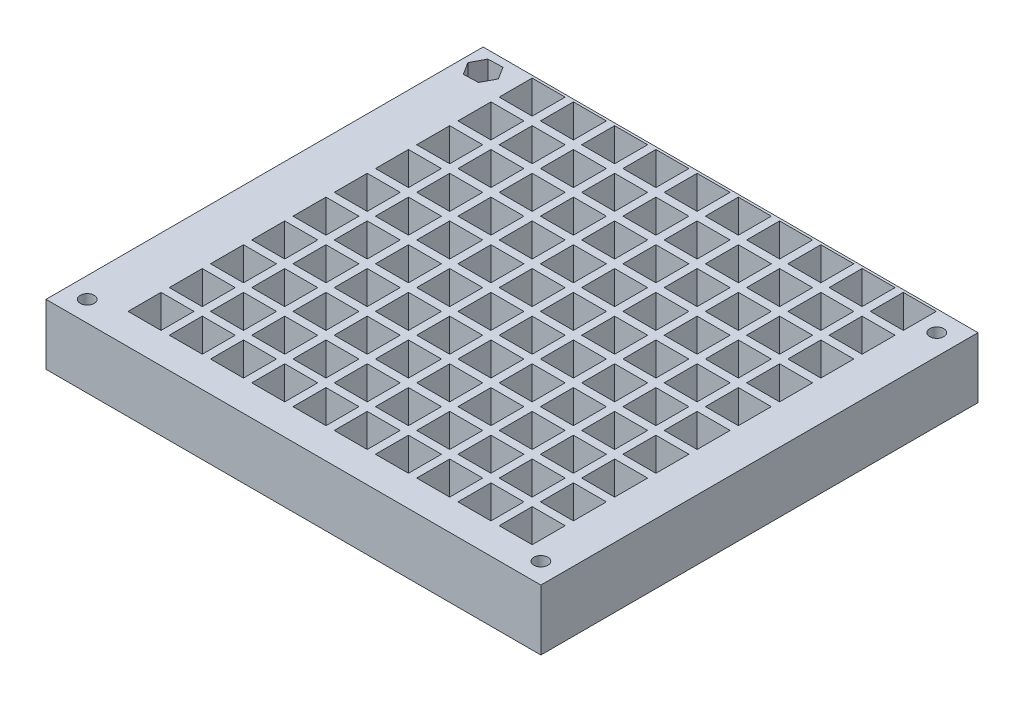
SolidWorks part; units mm, degrees
ref_plane "Front Plane" through (0, 0, 0) normal (0, 0, 1) x (1, 0, 0)
ref_plane "Top Plane" through (0, 0, 0) normal (0, 1, 0) x (1, 0, 0)
ref_plane "Right Plane" through (0, 0, 0) normal (1, 0, 0) x (0, 0, -1)
sketch "Sketch1" plane through (0, 0, 0) normal (0, 1, 0) x (1, 0, 0)
  line L0 (115, 101) -> (5, 101) construction
  line L1 (0, 0) -> (120, 0)
  line L2 (0, 0) -> (0, 106)
  line L3 (0, 106) -> (120, 106)
  line L4 (120, 0) -> (120, 106)
  line L6 (115, 101) -> (115, 5) construction
  line L8 (6.8918, 97.9769) -> (8.564, 101.1268)
  line L9 (8.564, 101.1268) -> (6.6722, 104.1499)
  line L10 (6.6722, 104.1499) -> (3.1082, 104.0231)
  line L11 (3.1082, 104.0231) -> (1.436, 100.8732)
  line L12 (1.436, 100.8732) -> (3.3278, 97.8501)
  line L13 (3.3278, 97.8501) -> (6.8918, 97.9769)
  line L14 (22.4764, 15.4138) -> (22.4764, 7.4138)
  line L15 (12.4764, 15.4138) -> (20.4764, 15.4138)
  line L16 (12.4764, 15.4138) -> (12.4764, 7.4138)
  line L17 (12.4764, 7.4138) -> (20.4764, 7.4138)
  line L18 (20.4764, 15.4138) -> (20.4764, 7.4138)
  line L19 (22.4764, 15.4138) -> (30.4764, 15.4138)
  line L20 (30.4764, 15.4138) -> (30.4764, 7.4138)
  line L21 (22.4764, 7.4138) -> (30.4764, 7.4138)
  line L22 (32.4764, 15.4138) -> (32.4764, 7.4138)
  line L23 (32.4764, 15.4138) -> (40.4764, 15.4138)
  line L24 (40.4764, 15.4138) -> (40.4764, 7.4138)
  line L25 (32.4764, 7.4138) -> (40.4764, 7.4138)
  line L26 (42.4764, 15.4138) -> (42.4764, 7.4138)
  line L27 (42.4764, 15.4138) -> (50.4764, 15.4138)
  line L28 (50.4764, 15.4138) -> (50.4764, 7.4138)
  line L29 (42.4764, 7.4138) -> (50.4764, 7.4138)
  line L30 (52.4764, 15.4138) -> (52.4764, 7.4138)
  line L31 (52.4764, 15.4138) -> (60.4764, 15.4138)
  line L32 (60.4764, 15.4138) -> (60.4764, 7.4138)
  line L33 (52.4764, 7.4138) -> (60.4764, 7.4138)
  line L34 (62.4764, 15.4138) -> (62.4764, 7.4138)
  line L35 (62.4764, 15.4138) -> (70.4764, 15.4138)
  line L36 (70.4764, 15.4138) -> (70.4764, 7.4138)
  line L37 (62.4764, 7.4138) -> (70.4764, 7.4138)
  line L38 (72.4764, 15.4138) -> (72.4764, 7.4138)
  line L39 (72.4764, 15.4138) -> (80.4764, 15.4138)
  line L40 (80.4764, 15.4138) -> (80.4764, 7.4138)
  line L41 (72.4764, 7.4138) -> (80.4764, 7.4138)
  line L42 (82.4764, 15.4138) -> (82.4764, 7.4138)
  line L43 (82.4764, 15.4138) -> (90.4764, 15.4138)
  line L44 (90.4764, 15.4138) -> (90.4764, 7.4138)
  line L45 (82.4764, 7.4138) -> (90.4764, 7.4138)
  line L46 (92.4764, 15.4138) -> (92.4764, 7.4138)
  line L47 (92.4764, 15.4138) -> (100.4764, 15.4138)
  line L48 (100.4764, 15.4138) -> (100.4764, 7.4138)
  line L49 (92.4764, 7.4138) -> (100.4764, 7.4138)
  line L50 (102.4764, 15.4138) -> (102.4764, 7.4138)
  line L51 (102.4764, 15.4138) -> (110.4764, 15.4138)
  line L52 (110.4764, 15.4138) -> (110.4764, 7.4138)
  line L53 (102.4764, 7.4138) -> (110.4764, 7.4138)
  line L54 (22.4764, 25.4138) -> (22.4764, 17.4138)
  line L55 (22.4764, 25.4138) -> (30.4764, 25.4138)
  line L56 (30.4764, 25.4138) -> (30.4764, 17.4138)
  line L57 (22.4764, 17.4138) -> (30.4764, 17.4138)
  line L58 (32.4764, 25.4138) -> (32.4764, 17.4138)
  line L59 (32.4764, 25.4138) -> (40.4764, 25.4138)
  line L60 (40.4764, 25.4138) -> (40.4764, 17.4138)
  line L61 (32.4764, 17.4138) -> (40.4764, 17.4138)
  line L62 (42.4764, 25.4138) -> (42.4764, 17.4138)
  line L63 (42.4764, 25.4138) -> (50.4764, 25.4138)
  line L64 (50.4764, 25.4138) -> (50.4764, 17.4138)
  line L65 (42.4764, 17.4138) -> (50.4764, 17.4138)
  line L66 (52.4764, 25.4138) -> (52.4764, 17.4138)
  line L67 (52.4764, 25.4138) -> (60.4764, 25.4138)
  line L68 (60.4764, 25.4138) -> (60.4764, 17.4138)
  line L69 (52.4764, 17.4138) -> (60.4764, 17.4138)
  line L70 (62.4764, 25.4138) -> (62.4764, 17.4138)
  line L71 (62.4764, 25.4138) -> (70.4764, 25.4138)
  line L72 (70.4764, 25.4138) -> (70.4764, 17.4138)
  line L73 (62.4764, 17.4138) -> (70.4764, 17.4138)
  line L74 (72.4764, 25.4138) -> (72.4764, 17.4138)
  line L75 (72.4764, 25.4138) -> (80.4764, 25.4138)
  line L76 (80.4764, 25.4138) -> (80.4764, 17.4138)
  line L77 (72.4764, 17.4138) -> (80.4764, 17.4138)
  line L78 (82.4764, 25.4138) -> (82.4764, 17.4138)
  line L79 (82.4764, 25.4138) -> (90.4764, 25.4138)
  line L80 (90.4764, 25.4138) -> (90.4764, 17.4138)
  line L81 (82.4764, 17.4138) -> (90.4764, 17.4138)
  line L82 (92.4764, 25.4138) -> (92.4764, 17.4138)
  line L83 (92.4764, 25.4138) -> (100.4764, 25.4138)
  line L84 (100.4764, 25.4138) -> (100.4764, 17.4138)
  line L85 (92.4764, 17.4138) -> (100.4764, 17.4138)
  line L86 (102.4764, 25.4138) -> (102.4764, 17.4138)
  line L87 (102.4764, 25.4138) -> (110.4764, 25.4138)
  line L88 (110.4764, 25.4138) -> (110.4764, 17.4138)
  line L89 (102.4764, 17.4138) -> (110.4764, 17.4138)
  line L90 (22.4764, 35.4138) -> (22.4764, 27.4138)
  line L91 (22.4764, 35.4138) -> (30.4764, 35.4138)
  line L92 (30.4764, 35.4138) -> (30.4764, 27.4138)
  line L93 (22.4764, 27.4138) -> (30.4764, 27.4138)
  line L94 (32.4764, 35.4138) -> (32.4764, 27.4138)
  line L95 (32.4764, 35.4138) -> (40.4764, 35.4138)
  line L96 (40.4764, 35.4138) -> (40.4764, 27.4138)
  line L97 (32.4764, 27.4138) -> (40.4764, 27.4138)
  line L98 (42.4764, 35.4138) -> (42.4764, 27.4138)
  line L99 (42.4764, 35.4138) -> (50.4764, 35.4138)
  line L100 (50.4764, 35.4138) -> (50.4764, 27.4138)
  line L101 (42.4764, 27.4138) -> (50.4764, 27.4138)
  line L102 (52.4764, 35.4138) -> (52.4764, 27.4138)
  line L103 (52.4764, 35.4138) -> (60.4764, 35.4138)
  line L104 (60.4764, 35.4138) -> (60.4764, 27.4138)
  line L105 (52.4764, 27.4138) -> (60.4764, 27.4138)
  line L106 (62.4764, 35.4138) -> (62.4764, 27.4138)
  line L107 (62.4764, 35.4138) -> (70.4764, 35.4138)
  line L108 (70.4764, 35.4138) -> (70.4764, 27.4138)
  line L109 (62.4764, 27.4138) -> (70.4764, 27.4138)
  line L110 (72.4764, 35.4138) -> (72.4764, 27.4138)
  line L111 (72.4764, 35.4138) -> (80.4764, 35.4138)
  line L112 (80.4764, 35.4138) -> (80.4764, 27.4138)
  line L113 (72.4764, 27.4138) -> (80.4764, 27.4138)
  line L114 (82.4764, 35.4138) -> (82.4764, 27.4138)
  line L115 (82.4764, 35.4138) -> (90.4764, 35.4138)
  line L116 (90.4764, 35.4138) -> (90.4764, 27.4138)
  line L117 (82.4764, 27.4138) -> (90.4764, 27.4138)
  line L118 (92.4764, 35.4138) -> (92.4764, 27.4138)
  line L119 (92.4764, 35.4138) -> (100.4764, 35.4138)
  line L120 (100.4764, 35.4138) -> (100.4764, 27.4138)
  line L121 (92.4764, 27.4138) -> (100.4764, 27.4138)
  line L122 (102.4764, 35.4138) -> (102.4764, 27.4138)
  line L123 (102.4764, 35.4138) -> (110.4764, 35.4138)
  line L124 (110.4764, 35.4138) -> (110.4764, 27.4138)
  line L125 (102.4764, 27.4138) -> (110.4764, 27.4138)
  line L126 (22.4764, 45.4138) -> (22.4764, 37.4138)
  line L127 (22.4764, 45.4138) -> (30.4764, 45.4138)
  line L128 (30.4764, 45.4138) -> (30.4764, 37.4138)
  line L129 (22.4764, 37.4138) -> (30.4764, 37.4138)
  line L130 (32.4764, 45.4138) -> (32.4764, 37.4138)
  line L131 (32.4764, 45.4138) -> (40.4764, 45.4138)
  line L132 (40.4764, 45.4138) -> (40.4764, 37.4138)
  line L133 (32.4764, 37.4138) -> (40.4764, 37.4138)
  line L134 (42.4764, 45.4138) -> (42.4764, 37.4138)
  line L135 (42.4764, 45.4138) -> (50.4764, 45.4138)
  line L136 (50.4764, 45.4138) -> (50.4764, 37.4138)
  line L137 (42.4764, 37.4138) -> (50.4764, 37.4138)
  line L138 (52.4764, 45.4138) -> (52.4764, 37.4138)
  line L139 (52.4764, 45.4138) -> (60.4764, 45.4138)
  line L140 (60.4764, 45.4138) -> (60.4764, 37.4138)
  line L141 (52.4764, 37.4138) -> (60.4764, 37.4138)
  line L142 (62.4764, 45.4138) -> (62.4764, 37.4138)
  line L143 (62.4764, 45.4138) -> (70.4764, 45.4138)
  line L144 (70.4764, 45.4138) -> (70.4764, 37.4138)
  line L145 (62.4764, 37.4138) -> (70.4764, 37.4138)
  line L146 (72.4764, 45.4138) -> (72.4764, 37.4138)
  line L147 (72.4764, 45.4138) -> (80.4764, 45.4138)
  line L148 (80.4764, 45.4138) -> (80.4764, 37.4138)
  line L149 (72.4764, 37.4138) -> (80.4764, 37.4138)
  line L150 (82.4764, 45.4138) -> (82.4764, 37.4138)
  line L151 (82.4764, 45.4138) -> (90.4764, 45.4138)
  line L152 (90.4764, 45.4138) -> (90.4764, 37.4138)
  line L153 (82.4764, 37.4138) -> (90.4764, 37.4138)
  line L154 (92.4764, 45.4138) -> (92.4764, 37.4138)
  line L155 (92.4764, 45.4138) -> (100.4764, 45.4138)
  line L156 (100.4764, 45.4138) -> (100.4764, 37.4138)
  line L157 (92.4764, 37.4138) -> (100.4764, 37.4138)
  line L158 (102.4764, 45.4138) -> (102.4764, 37.4138)
  line L159 (102.4764, 45.4138) -> (110.4764, 45.4138)
  line L160 (110.4764, 45.4138) -> (110.4764, 37.4138)
  line L161 (102.4764, 37.4138) -> (110.4764, 37.4138)
  line L162 (22.4764, 55.4138) -> (22.4764, 47.4138)
  line L163 (22.4764, 55.4138) -> (30.4764, 55.4138)
  line L164 (30.4764, 55.4138) -> (30.4764, 47.4138)
  line L165 (22.4764, 47.4138) -> (30.4764, 47.4138)
  line L166 (32.4764, 55.4138) -> (32.4764, 47.4138)
  line L167 (32.4764, 55.4138) -> (40.4764, 55.4138)
  line L168 (40.4764, 55.4138) -> (40.4764, 47.4138)
  line L169 (32.4764, 47.4138) -> (40.4764, 47.4138)
  line L170 (42.4764, 55.4138) -> (42.4764, 47.4138)
  line L171 (42.4764, 55.4138) -> (50.4764, 55.4138)
  line L172 (50.4764, 55.4138) -> (50.4764, 47.4138)
  line L173 (42.4764, 47.4138) -> (50.4764, 47.4138)
  line L174 (52.4764, 55.4138) -> (52.4764, 47.4138)
  line L175 (52.4764, 55.4138) -> (60.4764, 55.4138)
  line L176 (60.4764, 55.4138) -> (60.4764, 47.4138)
  line L177 (52.4764, 47.4138) -> (60.4764, 47.4138)
  line L178 (62.4764, 55.4138) -> (62.4764, 47.4138)
  line L179 (62.4764, 55.4138) -> (70.4764, 55.4138)
  line L180 (70.4764, 55.4138) -> (70.4764, 47.4138)
  line L181 (62.4764, 47.4138) -> (70.4764, 47.4138)
  line L182 (72.4764, 55.4138) -> (72.4764, 47.4138)
  line L183 (72.4764, 55.4138) -> (80.4764, 55.4138)
  line L184 (80.4764, 55.4138) -> (80.4764, 47.4138)
  line L185 (72.4764, 47.4138) -> (80.4764, 47.4138)
  line L186 (82.4764, 55.4138) -> (82.4764, 47.4138)
  line L187 (82.4764, 55.4138) -> (90.4764, 55.4138)
  line L188 (90.4764, 55.4138) -> (90.4764, 47.4138)
  line L189 (82.4764, 47.4138) -> (90.4764, 47.4138)
  line L190 (92.4764, 55.4138) -> (92.4764, 47.4138)
  line L191 (92.4764, 55.4138) -> (100.4764, 55.4138)
  line L192 (100.4764, 55.4138) -> (100.4764, 47.4138)
  line L193 (92.4764, 47.4138) -> (100.4764, 47.4138)
  line L194 (102.4764, 55.4138) -> (102.4764, 47.4138)
  line L195 (102.4764, 55.4138) -> (110.4764, 55.4138)
  line L196 (110.4764, 55.4138) -> (110.4764, 47.4138)
  line L197 (102.4764, 47.4138) -> (110.4764, 47.4138)
  line L198 (22.4764, 65.4138) -> (22.4764, 57.4138)
  line L199 (22.4764, 65.4138) -> (30.4764, 65.4138)
  line L200 (30.4764, 65.4138) -> (30.4764, 57.4138)
  line L201 (22.4764, 57.4138) -> (30.4764, 57.4138)
  line L202 (32.4764, 65.4138) -> (32.4764, 57.4138)
  line L203 (32.4764, 65.4138) -> (40.4764, 65.4138)
  line L204 (40.4764, 65.4138) -> (40.4764, 57.4138)
  line L205 (32.4764, 57.4138) -> (40.4764, 57.4138)
  line L206 (42.4764, 65.4138) -> (42.4764, 57.4138)
  line L207 (42.4764, 65.4138) -> (50.4764, 65.4138)
  line L208 (50.4764, 65.4138) -> (50.4764, 57.4138)
  line L209 (42.4764, 57.4138) -> (50.4764, 57.4138)
  line L210 (52.4764, 65.4138) -> (52.4764, 57.4138)
  line L211 (52.4764, 65.4138) -> (60.4764, 65.4138)
  line L212 (60.4764, 65.4138) -> (60.4764, 57.4138)
  line L213 (52.4764, 57.4138) -> (60.4764, 57.4138)
  line L214 (62.4764, 65.4138) -> (62.4764, 57.4138)
  line L215 (62.4764, 65.4138) -> (70.4764, 65.4138)
  line L216 (70.4764, 65.4138) -> (70.4764, 57.4138)
  line L217 (62.4764, 57.4138) -> (70.4764, 57.4138)
  line L218 (72.4764, 65.4138) -> (72.4764, 57.4138)
  line L219 (72.4764, 65.4138) -> (80.4764, 65.4138)
  line L220 (80.4764, 65.4138) -> (80.4764, 57.4138)
  line L221 (72.4764, 57.4138) -> (80.4764, 57.4138)
  line L222 (82.4764, 65.4138) -> (82.4764, 57.4138)
  line L223 (82.4764, 65.4138) -> (90.4764, 65.4138)
  line L224 (90.4764, 65.4138) -> (90.4764, 57.4138)
  line L225 (82.4764, 57.4138) -> (90.4764, 57.4138)
  line L226 (92.4764, 65.4138) -> (92.4764, 57.4138)
  line L227 (92.4764, 65.4138) -> (100.4764, 65.4138)
  line L228 (100.4764, 65.4138) -> (100.4764, 57.4138)
  line L229 (92.4764, 57.4138) -> (100.4764, 57.4138)
  line L230 (102.4764, 65.4138) -> (102.4764, 57.4138)
  line L231 (102.4764, 65.4138) -> (110.4764, 65.4138)
  line L232 (110.4764, 65.4138) -> (110.4764, 57.4138)
  line L233 (102.4764, 57.4138) -> (110.4764, 57.4138)
  line L234 (22.4764, 75.4138) -> (22.4764, 67.4138)
  line L235 (22.4764, 75.4138) -> (30.4764, 75.4138)
  line L236 (30.4764, 75.4138) -> (30.4764, 67.4138)
  line L237 (22.4764, 67.4138) -> (30.4764, 67.4138)
  line L238 (32.4764, 75.4138) -> (32.4764, 67.4138)
  line L239 (32.4764, 75.4138) -> (40.4764, 75.4138)
  line L240 (40.4764, 75.4138) -> (40.4764, 67.4138)
  line L241 (32.4764, 67.4138) -> (40.4764, 67.4138)
  line L242 (42.4764, 75.4138) -> (42.4764, 67.4138)
  line L243 (42.4764, 75.4138) -> (50.4764, 75.4138)
  line L244 (50.4764, 75.4138) -> (50.4764, 67.4138)
  line L245 (42.4764, 67.4138) -> (50.4764, 67.4138)
  line L246 (52.4764, 75.4138) -> (52.4764, 67.4138)
  line L247 (52.4764, 75.4138) -> (60.4764, 75.4138)
  line L248 (60.4764, 75.4138) -> (60.4764, 67.4138)
  line L249 (52.4764, 67.4138) -> (60.4764, 67.4138)
  line L250 (62.4764, 75.4138) -> (62.4764, 67.4138)
  line L251 (62.4764, 75.4138) -> (70.4764, 75.4138)
  line L252 (70.4764, 75.4138) -> (70.4764, 67.4138)
  line L253 (62.4764, 67.4138) -> (70.4764, 67.4138)
  line L254 (72.4764, 75.4138) -> (72.4764, 67.4138)
  line L255 (72.4764, 75.4138) -> (80.4764, 75.4138)
  line L256 (80.4764, 75.4138) -> (80.4764, 67.4138)
  line L257 (72.4764, 67.4138) -> (80.4764, 67.4138)
  line L258 (82.4764, 75.4138) -> (82.4764, 67.4138)
  line L259 (82.4764, 75.4138) -> (90.4764, 75.4138)
  line L260 (90.4764, 75.4138) -> (90.4764, 67.4138)
  line L261 (82.4764, 67.4138) -> (90.4764, 67.4138)
  line L262 (92.4764, 75.4138) -> (92.4764, 67.4138)
  line L263 (92.4764, 75.4138) -> (100.4764, 75.4138)
  line L264 (100.4764, 75.4138) -> (100.4764, 67.4138)
  line L265 (92.4764, 67.4138) -> (100.4764, 67.4138)
  line L266 (102.4764, 75.4138) -> (102.4764, 67.4138)
  line L267 (102.4764, 75.4138) -> (110.4764, 75.4138)
  line L268 (110.4764, 75.4138) -> (110.4764, 67.4138)
  line L269 (102.4764, 67.4138) -> (110.4764, 67.4138)
  line L270 (22.4764, 85.4138) -> (22.4764, 77.4138)
  line L271 (22.4764, 85.4138) -> (30.4764, 85.4138)
  line L272 (30.4764, 85.4138) -> (30.4764, 77.4138)
  line L273 (22.4764, 77.4138) -> (30.4764, 77.4138)
  line L274 (32.4764, 85.4138) -> (32.4764, 77.4138)
  line L275 (32.4764, 85.4138) -> (40.4764, 85.4138)
  line L276 (40.4764, 85.4138) -> (40.4764, 77.4138)
  line L277 (32.4764, 77.4138) -> (40.4764, 77.4138)
  line L278 (42.4764, 85.4138) -> (42.4764, 77.4138)
  line L279 (42.4764, 85.4138) -> (50.4764, 85.4138)
  line L280 (50.4764, 85.4138) -> (50.4764, 77.4138)
  line L281 (42.4764, 77.4138) -> (50.4764, 77.4138)
  line L282 (52.4764, 85.4138) -> (52.4764, 77.4138)
  line L283 (52.4764, 85.4138) -> (60.4764, 85.4138)
  line L284 (60.4764, 85.4138) -> (60.4764, 77.4138)
  line L285 (52.4764, 77.4138) -> (60.4764, 77.4138)
  line L286 (62.4764, 85.4138) -> (62.4764, 77.4138)
  line L287 (62.4764, 85.4138) -> (70.4764, 85.4138)
  line L288 (70.4764, 85.4138) -> (70.4764, 77.4138)
  line L289 (62.4764, 77.4138) -> (70.4764, 77.4138)
  line L290 (72.4764, 85.4138) -> (72.4764, 77.4138)
  line L291 (72.4764, 85.4138) -> (80.4764, 85.4138)
  line L292 (80.4764, 85.4138) -> (80.4764, 77.4138)
  line L293 (72.4764, 77.4138) -> (80.4764, 77.4138)
  line L294 (82.4764, 85.4138) -> (82.4764, 77.4138)
  line L295 (82.4764, 85.4138) -> (90.4764, 85.4138)
  line L296 (90.4764, 85.4138) -> (90.4764, 77.4138)
  line L297 (82.4764, 77.4138) -> (90.4764, 77.4138)
  line L298 (92.4764, 85.4138) -> (92.4764, 77.4138)
  line L299 (92.4764, 85.4138) -> (100.4764, 85.4138)
  line L300 (100.4764, 85.4138) -> (100.4764, 77.4138)
  line L301 (92.4764, 77.4138) -> (100.4764, 77.4138)
  line L302 (102.4764, 85.4138) -> (102.4764, 77.4138)
  line L303 (102.4764, 85.4138) -> (110.4764, 85.4138)
  line L304 (110.4764, 85.4138) -> (110.4764, 77.4138)
  line L305 (102.4764, 77.4138) -> (110.4764, 77.4138)
  line L306 (22.4764, 95.4138) -> (22.4764, 87.4138)
  line L307 (22.4764, 95.4138) -> (30.4764, 95.4138)
  line L308 (30.4764, 95.4138) -> (30.4764, 87.4138)
  line L309 (22.4764, 87.4138) -> (30.4764, 87.4138)
  line L310 (32.4764, 95.4138) -> (32.4764, 87.4138)
  line L311 (32.4764, 95.4138) -> (40.4764, 95.4138)
  line L312 (40.4764, 95.4138) -> (40.4764, 87.4138)
  line L313 (32.4764, 87.4138) -> (40.4764, 87.4138)
  line L314 (42.4764, 95.4138) -> (42.4764, 87.4138)
  line L315 (42.4764, 95.4138) -> (50.4764, 95.4138)
  line L316 (50.4764, 95.4138) -> (50.4764, 87.4138)
  line L317 (42.4764, 87.4138) -> (50.4764, 87.4138)
  line L318 (52.4764, 95.4138) -> (52.4764, 87.4138)
  line L319 (52.4764, 95.4138) -> (60.4764, 95.4138)
  line L320 (60.4764, 95.4138) -> (60.4764, 87.4138)
  line L321 (52.4764, 87.4138) -> (60.4764, 87.4138)
  line L322 (62.4764, 95.4138) -> (62.4764, 87.4138)
  line L323 (62.4764, 95.4138) -> (70.4764, 95.4138)
  line L324 (70.4764, 95.4138) -> (70.4764, 87.4138)
  line L325 (62.4764, 87.4138) -> (70.4764, 87.4138)
  line L326 (72.4764, 95.4138) -> (72.4764, 87.4138)
  line L327 (72.4764, 95.4138) -> (80.4764, 95.4138)
  line L328 (80.4764, 95.4138) -> (80.4764, 87.4138)
  line L329 (72.4764, 87.4138) -> (80.4764, 87.4138)
  line L330 (82.4764, 95.4138) -> (82.4764, 87.4138)
  line L331 (82.4764, 95.4138) -> (90.4764, 95.4138)
  line L332 (90.4764, 95.4138) -> (90.4764, 87.4138)
  line L333 (82.4764, 87.4138) -> (90.4764, 87.4138)
  line L334 (92.4764, 95.4138) -> (92.4764, 87.4138)
  line L335 (92.4764, 95.4138) -> (100.4764, 95.4138)
  line L336 (100.4764, 95.4138) -> (100.4764, 87.4138)
  line L337 (92.4764, 87.4138) -> (100.4764, 87.4138)
  line L338 (102.4764, 95.4138) -> (102.4764, 87.4138)
  line L339 (102.4764, 95.4138) -> (110.4764, 95.4138)
  line L340 (110.4764, 95.4138) -> (110.4764, 87.4138)
  line L341 (102.4764, 87.4138) -> (110.4764, 87.4138)
  line L342 (22.4764, 105.4138) -> (22.4764, 97.4138)
  line L343 (22.4764, 105.4138) -> (30.4764, 105.4138)
  line L344 (30.4764, 105.4138) -> (30.4764, 97.4138)
  line L345 (22.4764, 97.4138) -> (30.4764, 97.4138)
  line L346 (32.4764, 105.4138) -> (32.4764, 97.4138)
  line L347 (32.4764, 105.4138) -> (40.4764, 105.4138)
  line L348 (40.4764, 105.4138) -> (40.4764, 97.4138)
  line L349 (32.4764, 97.4138) -> (40.4764, 97.4138)
  line L350 (42.4764, 105.4138) -> (42.4764, 97.4138)
  line L351 (42.4764, 105.4138) -> (50.4764, 105.4138)
  line L352 (50.4764, 105.4138) -> (50.4764, 97.4138)
  line L353 (42.4764, 97.4138) -> (50.4764, 97.4138)
  line L354 (52.4764, 105.4138) -> (52.4764, 97.4138)
  line L355 (52.4764, 105.4138) -> (60.4764, 105.4138)
  line L356 (60.4764, 105.4138) -> (60.4764, 97.4138)
  line L357 (52.4764, 97.4138) -> (60.4764, 97.4138)
  line L358 (62.4764, 105.4138) -> (62.4764, 97.4138)
  line L359 (62.4764, 105.4138) -> (70.4764, 105.4138)
  line L360 (70.4764, 105.4138) -> (70.4764, 97.4138)
  line L361 (62.4764, 97.4138) -> (70.4764, 97.4138)
  line L362 (72.4764, 105.4138) -> (72.4764, 97.4138)
  line L363 (72.4764, 105.4138) -> (80.4764, 105.4138)
  line L364 (80.4764, 105.4138) -> (80.4764, 97.4138)
  line L365 (72.4764, 97.4138) -> (80.4764, 97.4138)
  line L366 (82.4764, 105.4138) -> (82.4764, 97.4138)
  line L367 (82.4764, 105.4138) -> (90.4764, 105.4138)
  line L368 (90.4764, 105.4138) -> (90.4764, 97.4138)
  line L369 (82.4764, 97.4138) -> (90.4764, 97.4138)
  line L370 (92.4764, 105.4138) -> (92.4764, 97.4138)
  line L371 (92.4764, 105.4138) -> (100.4764, 105.4138)
  line L372 (100.4764, 105.4138) -> (100.4764, 97.4138)
  line L373 (92.4764, 97.4138) -> (100.4764, 97.4138)
  line L374 (102.4764, 105.4138) -> (102.4764, 97.4138)
  line L375 (102.4764, 105.4138) -> (110.4764, 105.4138)
  line L376 (110.4764, 105.4138) -> (110.4764, 97.4138)
  line L377 (102.4764, 97.4138) -> (110.4764, 97.4138)
  line L378 (12.4764, 25.4138) -> (12.4764, 17.4138)
  line L379 (12.4764, 25.4138) -> (20.4764, 25.4138)
  line L380 (20.4764, 25.4138) -> (20.4764, 17.4138)
  line L381 (12.4764, 17.4138) -> (20.4764, 17.4138)
  line L382 (12.4764, 35.4138) -> (12.4764, 27.4138)
  line L383 (12.4764, 35.4138) -> (20.4764, 35.4138)
  line L384 (20.4764, 35.4138) -> (20.4764, 27.4138)
  line L385 (12.4764, 27.4138) -> (20.4764, 27.4138)
  line L386 (12.4764, 45.4138) -> (12.4764, 37.4138)
  line L387 (12.4764, 45.4138) -> (20.4764, 45.4138)
  line L388 (20.4764, 45.4138) -> (20.4764, 37.4138)
  line L389 (12.4764, 37.4138) -> (20.4764, 37.4138)
  line L390 (12.4764, 55.4138) -> (12.4764, 47.4138)
  line L391 (12.4764, 55.4138) -> (20.4764, 55.4138)
  line L392 (20.4764, 55.4138) -> (20.4764, 47.4138)
  line L393 (12.4764, 47.4138) -> (20.4764, 47.4138)
  line L394 (12.4764, 65.4138) -> (12.4764, 57.4138)
  line L395 (12.4764, 65.4138) -> (20.4764, 65.4138)
  line L396 (20.4764, 65.4138) -> (20.4764, 57.4138)
  line L397 (12.4764, 57.4138) -> (20.4764, 57.4138)
  line L398 (12.4764, 75.4138) -> (12.4764, 67.4138)
  line L399 (12.4764, 75.4138) -> (20.4764, 75.4138)
  line L400 (20.4764, 75.4138) -> (20.4764, 67.4138)
  line L401 (12.4764, 67.4138) -> (20.4764, 67.4138)
  line L402 (12.4764, 85.4138) -> (12.4764, 77.4138)
  line L403 (12.4764, 85.4138) -> (20.4764, 85.4138)
  line L404 (20.4764, 85.4138) -> (20.4764, 77.4138)
  line L405 (12.4764, 77.4138) -> (20.4764, 77.4138)
  line L406 (12.4764, 95.4138) -> (12.4764, 87.4138)
  line L407 (12.4764, 95.4138) -> (20.4764, 95.4138)
  line L408 (20.4764, 95.4138) -> (20.4764, 87.4138)
  line L409 (12.4764, 87.4138) -> (20.4764, 87.4138)
  line L410 (12.4764, 105.4138) -> (12.4764, 97.4138)
  line L411 (12.4764, 105.4138) -> (20.4764, 105.4138)
  line L412 (20.4764, 105.4138) -> (20.4764, 97.4138)
  line L413 (12.4764, 97.4138) -> (20.4764, 97.4138)
  circle A28 centre (5, 5) radius 1.7
  circle A29 centre (5, 101) radius 1.7
  circle A30 centre (115, 101) radius 1.7
  circle A31 centre (115, 5) radius 1.7
  circle A129 centre (5, 101) radius 3.0885 construction
  point P7 (115, 53)
  point P9 (60, 101)
  point P10 (60, 106)
  point P20 (120, 53)
  dimension "D5" = 110
  dimension "D6" = 96
  dimension "D3" = 8
  dimension "D8" = 3.4
  dimension "D1" = 120
  dimension "D2" = 106
  dimension "D4" = 8
  dimension "D7" = 10
  dimension "D9" = 10
extrude "Boss-Extrude1" add sketch "Sketch1" along normal blind 14.7 contours L1 L4 L3 L2 region at (1.6011, 0, -53)
equation "\"o\"= 10mm"
equation "\"P\"= 10"
